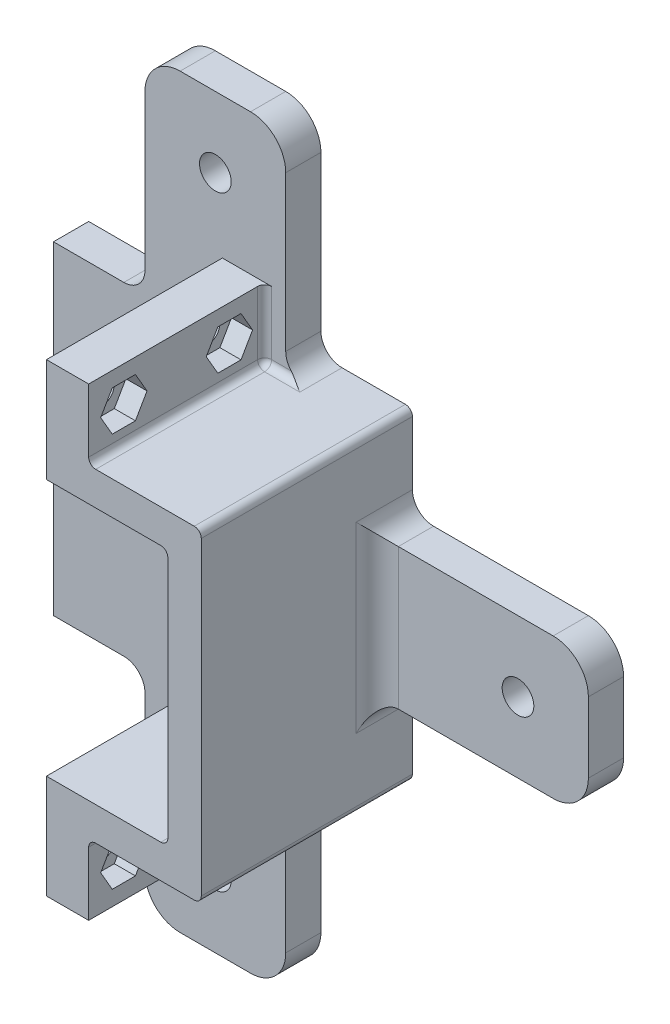
SolidWorks part; units mm, degrees
material "PBT General Purpose"
ref_plane "Front Plane" through (0, 0, 0) normal (0, 0, 1) x (1, 0, 0)
ref_plane "Top Plane" through (0, 0, 0) normal (0, 1, 0) x (1, 0, 0)
ref_plane "Right Plane" through (0, 0, 0) normal (1, 0, 0) x (0, 0, -1)
sketch "Sketch1" plane through (0, 0, 0) normal (0, 0, 1) x (1, 0, 0)
  line L0 (0, 0) -> (36, 0)
  line L1 (0, 0) -> (0, 36)
  line L2 (36, 0) -> (36, 36)
  line L3 (0, 36) -> (36, 36)
  line L4 (-5, 41) -> (41, 41)
  line L5 (-5, 41) -> (-5, -5)
  line L6 (41, 41) -> (41, -5)
  line L7 (-5, -5) -> (41, -5)
  dimension "D1" = 36
  dimension "D2" = 36
  dimension "D3" = 5
  dimension "D4" = 5
  dimension "D5" = 5
  dimension "D6" = 5
extrude "Boss-Extrude1" add sketch "Sketch1" along normal blind 25
sketch "Sketch3" plane through (0, 0, 0) normal (0, 0, -1) x (-1, 0, 0)
  line L0 (-41, 41) -> (5, 41) construction
  line L1 (-41, -5) -> (-41, 41) construction
  line L2 (5, 41) -> (5, -5) construction
  line L3 (5, -5) -> (-41, -5) construction
  line L4 (-41, 41) -> (5, 41)
  line L5 (-41, -5) -> (-41, 41)
  line L6 (5, 41) -> (5, -5)
  line L7 (5, -5) -> (-41, -5)
extrude "Boss-Extrude2" add sketch "Sketch3" along normal blind 5
sketch "Sketch4" plane through (0, 41, 0) normal (0, 1, 0) x (1, 0, 0)
  line L0 (28, 0) -> (28, 5)
  line L1 (28, 0) -> (8, 0)
  line L2 (28, 5) -> (8, 5)
  line L3 (8, 0) -> (8, 5)
  line L4 (-5, 5) -> (41, 5) construction
  line L5 (18, -25) -> (18, 5) construction
  line L6 (41, -25) -> (-5, -25) construction
  line L7 (18, 0) -> (18, 5) construction
  dimension "D1" = 5
  dimension "D2" = 20
extrude "Boss-Extrude3" add sketch "Sketch4" along normal blind 30
sketch "Sketch5" plane through (0, 0, 0) normal (0, 0, 1) x (1, 0, 0)
  line L0 (18, 71) -> (18, 41) construction
  line L1 (8, 71) -> (28, 71) construction
  line L2 (8, 41) -> (28, 41) construction
  circle A0 centre (18, 61) radius 2.25
  dimension "D1" = 10
  dimension "D2" = 4.5
extrude "Cut-Extrude1" cut sketch "Sketch5" against normal through all
sketch "Sketch6" plane through (0, 0, 25) normal (0, 0, 1) x (1, 0, 0)
  line L0 (-5, 18) -> (41, 18) construction
  line L1 (-5, 41) -> (-5, -5) construction
  line L2 (41, -5) -> (41, 41) construction
ref_plane "Plane1" through (0, 18, 0) normal (0, -1, 0) x (1, 0, 0)
mirror "Mirror1" about plane through (0, 18, 0) normal (0, -1, 0) of "Cut-Extrude1", "Boss-Extrude3"
sketch "Эскиз1" plane through (0, 0, 25) normal (0, 0, 1) x (1, 0, 0)
  line L0 (18, 41) -> (18, -5)
  line L3 (18, 41) -> (-5, 41)
  line L4 (18, -5) -> (-5, -5)
  line L5 (-5, 41) -> (-5, -5)
  line L6 (41, 41) -> (-5, 41) construction
  line L7 (-5, -5) -> (41, -5) construction
  line L8 (-5, 41) -> (-5, -5) construction
extrude "Вырез-Вытянуть1" cut sketch "Эскиз1" against normal up to surface (25 mm away) up to face at (20.25, -25, 0)
sketch "Эскиз3" plane through (18, 0, 0) normal (-1, 0, 0) x (0, 0, 1)
  line L0 (25, -5) -> (0, -5)
  line L1 (25, -5) -> (25, -15)
  line L2 (0, -5) -> (0, -15)
  line L3 (25, -15) -> (0, -15)
  dimension "D1" = 10
extrude "Бобышка-Вытянуть1" add sketch "Эскиз3" against normal blind 7
fillet "Скругление1" radius 1 1 edges at (25, -5, 12.5)
sketch "Эскиз4" plane through (18, 0, 0) normal (-1, 0, 0) x (0, 0, 1)
  line L0 (25, -10) -> (0, -10) construction
  line L1 (25, -15) -> (25, 0) construction
  line L2 (0, 0) -> (0, -15) construction
  line L3 (0, -15) -> (25, -15) construction
  circle A0 centre (20, -10) radius 1.6
  circle A1 centre (5, -10) radius 1.6
  dimension "D2" = 3.2
  dimension "D3" = 3.2
  dimension "D4" = 5
  dimension "D5" = 5
  dimension "D1" = 5
extrude "Вырез-Вытянуть2" cut sketch "Эскиз4" against normal through all
sketch "Эскиз5" plane through (25, 0, 0) normal (1, 0, 0) x (0, 0, -1)
  line L0 (-20, -10) -> (-5, -10) construction
  line L1 (-18.3546, -12.85) -> (-16.7091, -10)
  line L2 (-16.7091, -10) -> (-18.3546, -7.15)
  line L3 (-18.3546, -7.15) -> (-21.6454, -7.15)
  line L4 (-21.6454, -7.15) -> (-23.2909, -10)
  line L5 (-23.2909, -10) -> (-21.6454, -12.85)
  line L6 (-21.6454, -12.85) -> (-18.3546, -12.85)
  line L7 (-6.6454, -12.85) -> (-3.3546, -12.85)
  line L8 (-3.3546, -12.85) -> (-1.7091, -10)
  line L9 (-1.7091, -10) -> (-3.3546, -7.15)
  line L10 (-3.3546, -7.15) -> (-6.6454, -7.15)
  line L11 (-6.6454, -7.15) -> (-8.2909, -10)
  line L12 (-8.2909, -10) -> (-6.6454, -12.85)
  circle A0 centre (-20, -10) radius 2.85 construction
  circle A1 centre (-5, -10) radius 2.85 construction
  dimension "D1" = 5.7
  dimension "D2" = 5.7
extrude "Вырез-Вытянуть3" cut sketch "Эскиз5" against normal blind 3
mirror "Зеркальное отражение2" about plane through (0, 18, 0) normal (0, -1, 0) of "Бобышка-Вытянуть1"
mirror "Зеркальное отражение3" about plane through (0, 18, 0) normal (0, -1, 0) of "Вырез-Вытянуть2"
mirror "Зеркальное отражение4" about plane through (0, 18, 0) normal (0, -1, 0) of "Вырез-Вытянуть3"
sketch "Эскиз6" plane through (0, 0, 25) normal (0, 0, 1) x (1, 0, 0)
  line L0 (18, 36.25) -> (36.25, 36.25)
  line L1 (18, 36.25) -> (18, -0.25)
  line L2 (36.25, 36.25) -> (36.25, -0.25)
  line L3 (18, -0.25) -> (36.25, -0.25)
  line L4 (18, 36) -> (18, 51) construction
  line L5 (36, 0) -> (36, 36) construction
  line L6 (36, 36) -> (18, 36) construction
  line L7 (18, 0) -> (36, 0) construction
  dimension "D1" = 0.25
  dimension "D2" = 0.25
  dimension "D3" = 0.25
extrude "Вырез-Вытянуть4" cut sketch "Эскиз6" against normal up to surface (25 mm away) up to face at (19.2282, 16.867, 0)
fillet "Скругление2" radius 1 1 edges at (25, 41, 12.5)
fillet "Скругление3" radius 1 6 edges at (27, -5, 0) (25.2929, -5.2929, 0) (27, 41, 0) (25.2929, 41.2929, 0) (25, -10.5, 0) (25, 46.5, 0)
fillet "Скругление4" radius 5 4 edges at (8, -35, -2.5) (28, -35, -2.5) (8, 71, -2.5) (28, 71, -2.5)
fillet "Скругление6" radius 1 5 edges at (27.125, 36.25, 0) (36.25, 18, 0) (27.125, -0.25, 0) (36.25, -0.25, 12.5) (36.25, 36.25, 12.5)
sketch "Эскиз7" plane through (18, 0, 0) normal (-1, 0, 0) x (0, 0, 1)
  line L4 (0, 51) -> (0, 35.25)
  line L5 (1, 36.25) -> (25, 36.25)
  line L6 (25, 36.25) -> (25, 51)
  line L7 (25, 51) -> (0, 51)
  line L8 (0, 51) -> (0, 35.25)
  line L9 (1, 36.25) -> (25, 36.25)
  line L10 (25, 36.25) -> (25, 51)
  line L11 (25, 51) -> (0, 51)
  line L12 (25, -15) -> (25, -0.25)
  line L13 (25, -0.25) -> (1, -0.25)
  line L14 (0, 0.75) -> (0, -15)
  line L15 (0, -15) -> (25, -15)
  line L16 (25, -15) -> (25, -0.25)
  line L17 (25, -0.25) -> (1, -0.25)
  line L18 (0, 0.75) -> (0, -15)
  line L19 (0, -15) -> (25, -15)
  arc A1 (1, 36.25) -> (0, 35.25) centre (1, 35.25) ccw
  arc A2 (1, 36.25) -> (0, 35.25) centre (1, 35.25) ccw
  arc A3 (0, 0.75) -> (1, -0.25) centre (1, 0.75) ccw
  arc A4 (0, 0.75) -> (1, -0.25) centre (1, 0.75) ccw
  dimension "D1" = 0
  dimension "D2" = 0
extrude "Вырез-Вытянуть5" cut sketch "Эскиз7" against normal blind 1
sketch "Эскиз9" plane through (41, 0, 0) normal (1, 0, 0) x (0, 0, -1)
  line L0 (5, 18) -> (-13.0756, 18) construction
  line L1 (5, 41) -> (5, -5) construction
  line L2 (5, 8) -> (5, 28)
  line L3 (5, 8) -> (0, 8)
  line L4 (5, 28) -> (0, 28)
  line L5 (0, 8) -> (0, 28)
  line L6 (0, 18) -> (5, 18) construction
  dimension "D1" = 20
  dimension "D2" = 5
extrude "Бобышка-Вытянуть2" add sketch "Эскиз9" along normal blind 30
sketch "Эскиз10" plane through (0, 0, 0) normal (0, 0, 1) x (1, 0, 0)
  line L0 (71, 18) -> (41, 18) construction
  line L1 (71, 28) -> (71, 8) construction
  line L2 (41, 28) -> (41, 8) construction
  circle A0 centre (61, 18) radius 2.25
  dimension "D1" = 4.5
  dimension "D2" = 10
extrude "Вырез-Вытянуть6" cut sketch "Эскиз10" against normal through all
fillet "Скругление7" radius 5 2 edges at (71, 8, -2.5) (71, 28, -2.5)
fillet "Скругление8" radius 3 7 edges at (41, 18, 0)
fillet "Скругление9" radius 1 2 edges at (41, -5, 10) (41, 41, 10)
